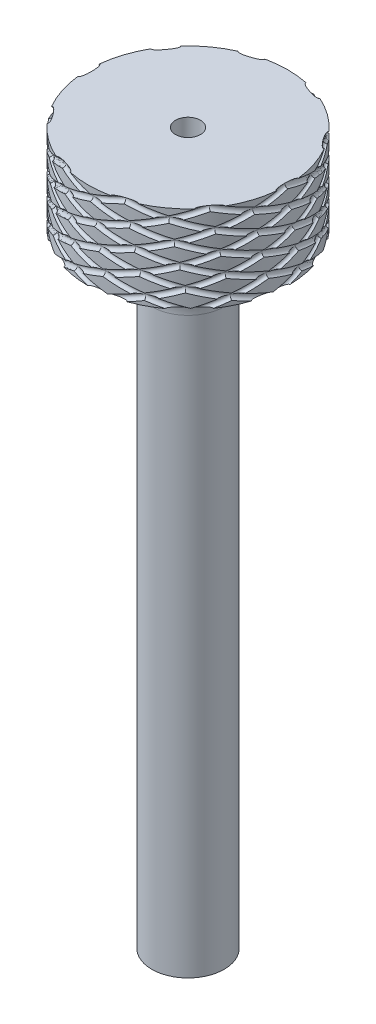
SolidWorks part; units mm, degrees
ref_plane "Front Plane" through (0, 0, 0) normal (0, 0, 1) x (1, 0, 0)
ref_plane "Top Plane" through (0, 0, 0) normal (0, 1, 0) x (1, 0, 0)
ref_plane "Right Plane" through (0, 0, 0) normal (1, 0, 0) x (0, 0, -1)
sketch "Sketch1" plane through (0, 0, 0) normal (0, 1, 0) x (1, 0, 0)
  circle A0 centre (0, 0) radius 2.9
  dimension "D1" = 5.8
extrude "Boss-Extrude1" add sketch "Sketch1" along normal blind 50
sketch "Sketch2" plane through (0, 50, 0) normal (0, 1, 0) x (1, 0, 0)
  circle A0 centre (0, 0) radius 8
extrude "Boss-Extrude2" add sketch "Sketch2" along normal blind 7
sketch "Sketch7" plane through (0, 0, 0) normal (0, -1, 0) x (1, 0, 0)
  circle A0 centre (0, 0) radius 1
  dimension "D1" = 2
extrude "Cut-Extrude1" cut sketch "Sketch7" against normal up to surface (57 mm away) up to face at (0, 57, 8)
fillet "Fillet1" radius 4 1 edges at (0, 50, 2.9)
sketch "Sketch5" plane through (0, 57, 0) normal (0, 1, 0) x (1, 0, 0)
  circle A0 centre (0, 0) radius 8
sketch "Sketch11" plane through (0, 57, 0) normal (0, 1, 0) x (1, 0, 0)
  circle A0 centre (0, 0) radius 8
curve "Helix/Spiral2" pitch 15 height 15 turns 1
sweep "Cut-Sweep2" cut path "Helix/Spiral2" parameters "D3"=0.5
pattern_circular "CirPattern2" count 10 over 360 about axis through (0, 59.8284, 0) along (0, -1, 0) of "Cut-Sweep2"
curve "Helix/Spiral3" pitch 17 height 17 turns 1
sweep "Cut-Sweep4" cut path "Helix/Spiral3" circular profile diameter 0.5 parameters "D3"=0.5
pattern_circular "CirPattern3" count 10 over 360 about axis through (0, 59.8284, 0) along (0, -1, 0) of "Cut-Sweep4"
